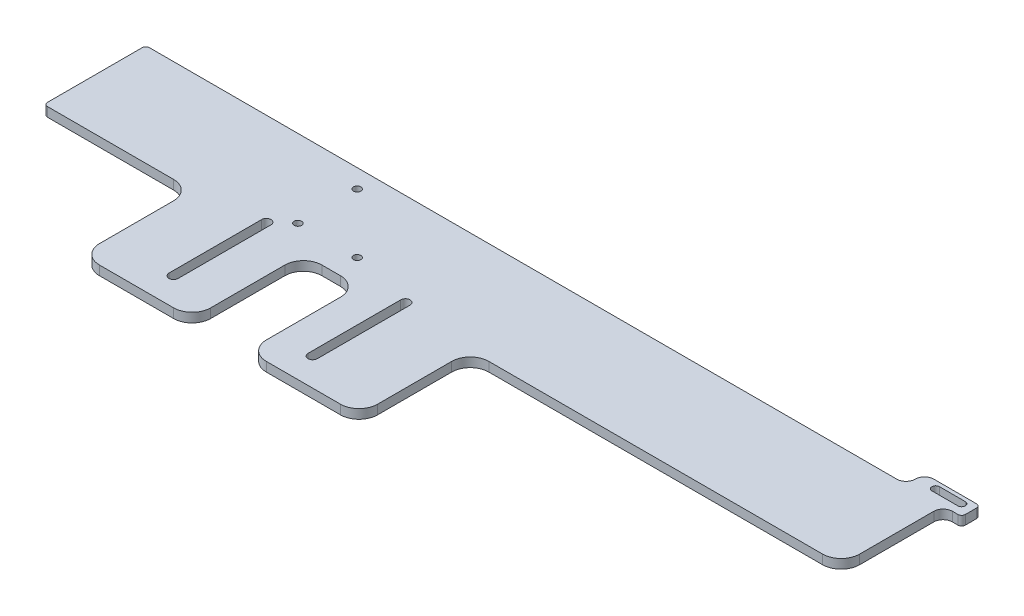
SolidWorks part; units mm, degrees
ref_plane "前视基准面" through (0, 0, 0) normal (0, 0, 1) x (1, 0, 0)
ref_plane "上视基准面" through (0, 0, 0) normal (0, 1, 0) x (1, 0, 0)
ref_plane "右视基准面" through (0, 0, 0) normal (1, 0, 0) x (0, 0, -1)
sketch "Sketch1" plane through (0, 0, 0) normal (0, 1, 0) x (1, 0, 0)
  line L0 (0, 0) -> (-130, 0)
  line L1 (-130, 0) -> (-130, -55)
  line L2 (-130, -55) -> (300, -55)
  line L3 (300, -55) -> (300, 0)
  line L4 (300, 0) -> (0, 0)
  line L5 (-71.8795, -26) -> (229.6661, -26) construction
  line L6 (10, 27.7242) -> (10, -77.6418) construction
  circle A0 centre (-6, -10) radius 2
  circle A1 centre (-6, -42) radius 2
  circle A2 centre (26, -42) radius 2
  dimension "D6" = 4
  dimension "D1" = 300
  dimension "D2" = 130
  dimension "D3" = 55
  dimension "D4" = 26
  dimension "D5" = 290
  dimension "D7" = 16
  dimension "D8" = 16
extrude "Boss-Extrude1" add sketch "Sketch1" along normal blind 5
sketch "Sketch2" plane through (0, 5, 0) normal (0, 1, 0) x (1, 0, 0)
  line L0 (280, 10) -> (280, 0)
  line L1 (280, 0) -> (310, 0)
  line L2 (310, 0) -> (310, 10)
  line L3 (310, 10) -> (280, 10)
  line L4 (300, -55) -> (300, 0) construction
  line L5 (300, 0) -> (-130, 0) construction
  dimension "D1" = 10
  dimension "D2" = 30
  dimension "D3" = 0
  dimension "D4" = 10
extrude "Boss-Extrude2" add sketch "Sketch2" against normal blind 5
sketch "Sketch3" plane through (0, 5, 0) normal (0, 1, 0) x (1, 0, 0)
  line L0 (-6, -42) -> (307.8629, -42) construction
  line L1 (-6, 6) -> (307.8629, 6) construction
  line L2 (290, 6) -> (304, 6) construction
  line L3 (290, 8) -> (304, 8)
  line L4 (290, 4) -> (304, 4)
  line L5 (300, -55) -> (300, 0) construction
  arc A0 (290, 8) -> (290, 4) centre (290, 6) ccw
  arc A1 (304, 4) -> (304, 8) centre (304, 6) ccw
  point P8 (297, 6)
  dimension "D2" = 2
  dimension "D3" = 4
  dimension "D4" = 10
  dimension "D1" = 48
extrude "Cut-Extrude1" cut sketch "Sketch3" against normal through all
fillet "Fillet1" radius 5 3 edges at (300, 2.5, 0) (280, 2.5, -10) (280, 2.5, 0)
sketch "Sketch4" plane through (0, 5, 0) normal (0, 1, 0) x (1, 0, 0)
  line L0 (70, -55) -> (70, -167.0676) construction
  line L1 (-130, -55) -> (300, -55) construction
  line L2 (-130, 0) -> (-130, -55) construction
  line L3 (40, -55) -> (40, -115)
  line L4 (100, -55) -> (100, -115)
  line L5 (40, -55) -> (100, -55)
  line L6 (40, -115) -> (100, -115)
  line L7 (25, 29.2403) -> (25, -140.6227) construction
  line L8 (40, -55) -> (40, -167.0676) construction
  line L9 (100, -55) -> (100, -167.0676) construction
  line L10 (10, -55) -> (-50, -55)
  line L11 (10, -55) -> (10, -115)
  line L12 (10, -115) -> (-50, -115)
  line L13 (-50, -55) -> (-50, -115)
  dimension "D1" = 200
  dimension "D4" = 60
  dimension "D5" = 25
  dimension "D2" = 30
  dimension "D3" = 30
extrude "Boss-Extrude3" add sketch "Sketch4" against normal blind 5
fillet "Fillet2" radius 10 4 edges at (100, 2.5, 55) (100, 2.5, 115) (40, 2.5, 115) (40, 2.5, 55)
fillet "Fillet3" radius 10 1 edges at (300, 2.5, 55)
fillet "Fillet4" radius 2 2 edges at (310, 2.5, 0) (310, 2.5, -10)
fillet "Fillet5" radius 2 2 edges at (-130, 2.5, 55) (-130, 2.5, 0)
fillet "Fillet6" radius 10 4 edges at (10, 2.5, 55) (-50, 2.5, 55) (10, 2.5, 115) (-50, 2.5, 115)
sketch "Sketch6" plane through (0, 5, 0) normal (0, 1, 0) x (1, 0, 0)
  line L0 (-15, -57.493) -> (-15, -135.3424) construction
  line L1 (60, -57.493) -> (60, -135.3424) construction
  line L2 (0, 0) -> (0, -145.9649) construction
  line L3 (-15, -100) -> (-15, -50) construction
  line L4 (-17.5, -100) -> (-17.5, -50)
  line L5 (-12.5, -100) -> (-12.5, -50)
  line L6 (60, -100) -> (60, -50) construction
  line L7 (57.5, -100) -> (57.5, -50)
  line L8 (62.5, -100) -> (62.5, -50)
  line L9 (-40, -115) -> (0, -115) construction
  line L10 (50, -115) -> (90, -115) construction
  arc A0 (-17.5, -100) -> (-12.5, -100) centre (-15, -100) ccw
  arc A1 (-12.5, -50) -> (-17.5, -50) centre (-15, -50) ccw
  arc A2 (57.5, -100) -> (62.5, -100) centre (60, -100) ccw
  arc A3 (62.5, -50) -> (57.5, -50) centre (60, -50) ccw
  point P9 (-15, -75)
  point P16 (60, -75)
  dimension "D3" = 2.5
  dimension "D4" = 2.5
  dimension "D1" = 15
  dimension "D2" = 60
  dimension "D5" = 15
  dimension "D6" = 15
  dimension "D7" = 50
  dimension "D8" = 50
extrude "Cut-Extrude2" cut sketch "Sketch6" against normal through all
